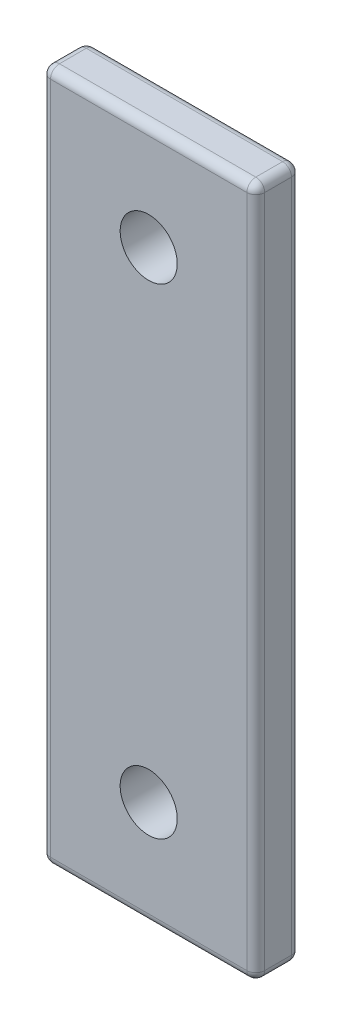
SolidWorks part; units mm, degrees
ref_plane "Front Plane" through (0, 0, 0) normal (0, 0, 1) x (1, 0, 0)
ref_plane "Top Plane" through (0, 0, 0) normal (0, 1, 0) x (1, 0, 0)
ref_plane "Right Plane" through (0, 0, 0) normal (1, 0, 0) x (0, 0, -1)
sketch "Sketch1" plane through (0, 0, 0) normal (0, 0, 1) x (1, 0, 0)
  line L1 (-24, -77.5) -> (24, -77.5)
  line L2 (-24, -77.5) -> (-24, 77.5)
  line L3 (-24, 77.5) -> (24, 77.5)
  line L4 (24, -77.5) -> (24, 77.5)
  line L5 (-24, -77.5) -> (24, 77.5) construction
  line L6 (-24, 77.5) -> (24, -77.5) construction
  point P0 (0, 0)
  dimension "D1" = 48
  dimension "D2" = 155
extrude "Boss-Extrude1" add sketch "Sketch1" along normal blind 10
fillet "Fillet1" radius 2 8 edges at (0, -77.5, 10) (-24, 0, 10) (0, 77.5, 10) (24, 0, 10) (0, 77.5, 0) (-24, 0, 0) (0, -77.5, 0) (24, 0, 0)
fillet "Fillet2" radius 2 12 edges at (23.4142, 76.9142, 9.4142) (23.4142, 76.9142, 0.5858) (23.4142, -76.9142, 9.4142) (23.4142, -76.9142, 0.5858) (-23.4142, -76.9142, 9.4142) (-23.4142, -76.9142, 0.5858) (-23.4142, 76.9142, 9.4142) (-23.4142, 76.9142, 0.5858) (24, 77.5, 5) (24, -77.5, 5) (-24, -77.5, 5) (-24, 77.5, 5)
sketch "Sketch2" plane through (0, 0, 0) normal (0, 0, -1) x (-1, 0, 0)
  line L0 (22, 75.5) -> (-22, 75.5) construction
  circle A0 centre (0, 53.85) radius 6.4
  dimension "D1" = 12.8
  dimension "D2" = 21.65
extrude "Cut-Extrude1" cut sketch "Sketch2" against normal through all
sketch "Sketch6" plane through (0, 0, 0) normal (0, 0, -1) x (-1, 0, 0)
  line L0 (-22, 0) -> (22, 0) construction
  line L1 (-22, 75.5) -> (-22, -75.5) construction
  line L2 (22, -75.5) -> (22, 75.5) construction
mirror "Mirror2" about plane through (0, 0, 0) normal (0, 1, 0) of "Cut-Extrude1"
